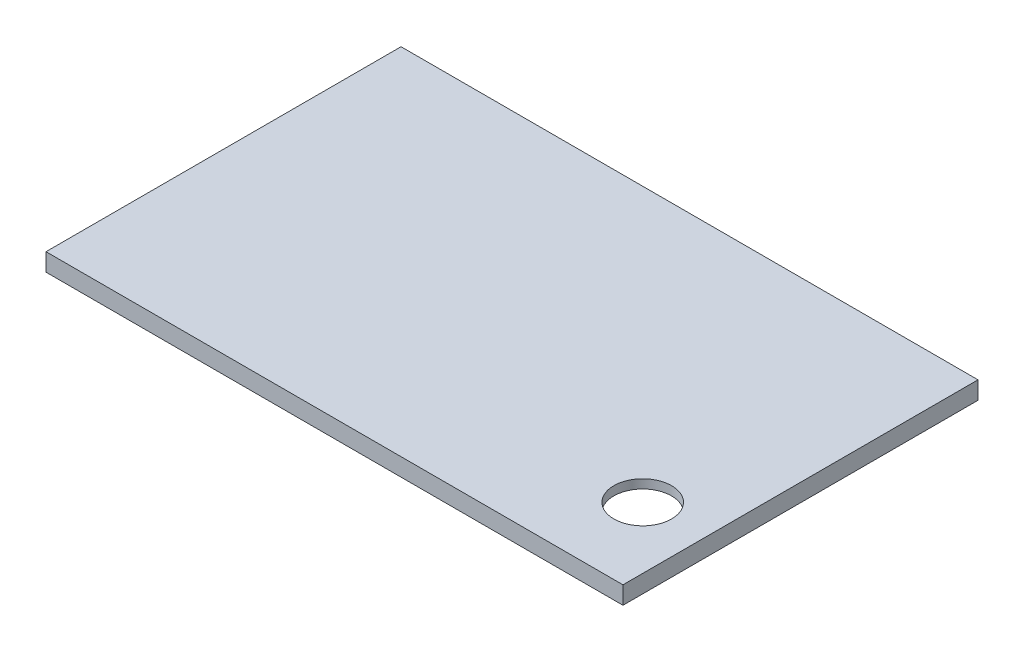
SolidWorks part; units mm, degrees
ref_plane "Front Plane" through (0, 0, 0) normal (0, 0, 1) x (1, 0, 0)
ref_plane "Top Plane" through (0, 0, 0) normal (0, 1, 0) x (1, 0, 0)
ref_plane "Right Plane" through (0, 0, 0) normal (1, 0, 0) x (0, 0, -1)
sketch "Sketch1" plane through (0, 0, 0) normal (0, 1, 0) x (1, 0, 0)
  line L1 (-32.5, -20) -> (32.5, -20)
  line L2 (-32.5, -20) -> (-32.5, 20)
  line L3 (-32.5, 20) -> (32.5, 20)
  line L4 (32.5, -20) -> (32.5, 20)
  line L5 (-32.5, -20) -> (32.5, 20) construction
  line L6 (-32.5, 20) -> (32.5, -20) construction
  point P0 (0, 0)
  dimension "D1" = 65
  dimension "D2" = 40
extrude "Boss-Extrude1" add sketch "Sketch1" along normal blind 45
shell "Shell1" thickness 1 removed face at (0, 45, 0)
sketch "Sketch2" plane through (32.5, 0, 0) normal (1, 0, 0) x (0, 0, -1)
  line L0 (0, 0) -> (0, 26)
  line L1 (0, 24.75) -> (0, -24.75) construction
  circle A0 centre (0, 26) radius 5
  dimension "D1" = 26
extrude "Cut-Extrude1" cut sketch "Sketch2" against normal blind 8 contours A0 region at (32.5, 22.5645, -3.4355)
sketch "Sketch3" plane through (0, 0, 0) normal (0, -1, 0) x (1, 0, 0)
  circle A0 centre (0, 0) radius 7.5
extrude "Cut-Extrude2" cut sketch "Sketch3" against normal blind 8
fillet "Fillet1" radius 2 5 edges at (0, 1, 19) (-31.5, 1, 0) (0, 1, -19) (31.5, 1, 0) (0, 1, -7.5)
fillet "Fillet2" radius 2.5 8 edges at (-30.9142, 1.5858, 18.4142) (-30.9142, 1.5858, -18.4142) (30.9142, 1.5858, -18.4142) (30.9142, 1.5858, 18.4142) (31.5, 24, 19) (31.5, 24, -19) (-31.5, 24, -19) (-31.5, 24, 19)
sketch "Sketch4" plane through (0, 45, 0) normal (0, 1, 0) x (1, 0, 0)
  line L8 (32.5, -20) -> (32.5, 20)
  line L9 (32.5, 20) -> (-32.5, 20)
  line L10 (-32.5, 20) -> (-32.5, -20)
  line L11 (-32.5, -20) -> (32.5, -20)
  line L12 (32.5, -20) -> (32.5, 20)
  line L13 (32.5, 20) -> (-32.5, 20)
  line L14 (-32.5, 20) -> (-32.5, -20)
  line L15 (-32.5, -20) -> (32.5, -20)
  dimension "D1" = 0
sketch "Sketch5" plane through (0, 0, 20) normal (0, 0, 1) x (1, 0, 0)
  line L0 (-32.5, 45) -> (-32.5, 0) construction
  line L1 (-32.5, 44) -> (34.3437, 44)
  line L2 (-32.5, 44) -> (-32.5, -2.5787)
  line L3 (-32.5, -2.5787) -> (34.3437, -2.5787)
  line L4 (34.3437, 44) -> (34.3437, -2.5787)
  line L5 (-32.5, 45) -> (32.5, 45) construction
  dimension "D1" = 1
extrude "Cut-Extrude3" cut sketch "Sketch5" against normal blind 250
sketch "Sketch6" plane through (0, 45, 0) normal (0, 1, 0) x (1, 0, 0)
  line L8 (31.51, -19.01) -> (31.51, 19.01)
  line L9 (31.51, 19.01) -> (-31.51, 19.01)
  line L10 (-31.51, 19.01) -> (-31.51, -19.01)
  line L11 (-31.51, -19.01) -> (31.51, -19.01)
  line L12 (31.51, -19.01) -> (31.51, 19.01)
  line L13 (31.51, 19.01) -> (-31.51, 19.01)
  line L14 (-31.51, 19.01) -> (-31.51, -19.01)
  line L15 (-31.51, -19.01) -> (31.51, -19.01)
  dimension "D1" = 0.99
sketch "Sketch7" plane through (0, 45, 0) normal (0, 1, 0) x (1, 0, 0)
  line L1 (-32.5, 20) -> (32.5, 20)
  line L2 (-32.5, 20) -> (-32.5, -20)
  line L3 (-32.5, -20) -> (32.5, -20)
  line L4 (32.5, 20) -> (32.5, -20)
extrude "Boss-Extrude3" add sketch "Sketch7" along normal blind 1
sketch "Sketch8" plane through (0, 46, 0) normal (0, 1, 0) x (1, 0, 0)
  circle A0 centre (25.5643, -10.8385) radius 3.25
extrude "Cut-Extrude4" cut sketch "Sketch8" against normal blind 7
